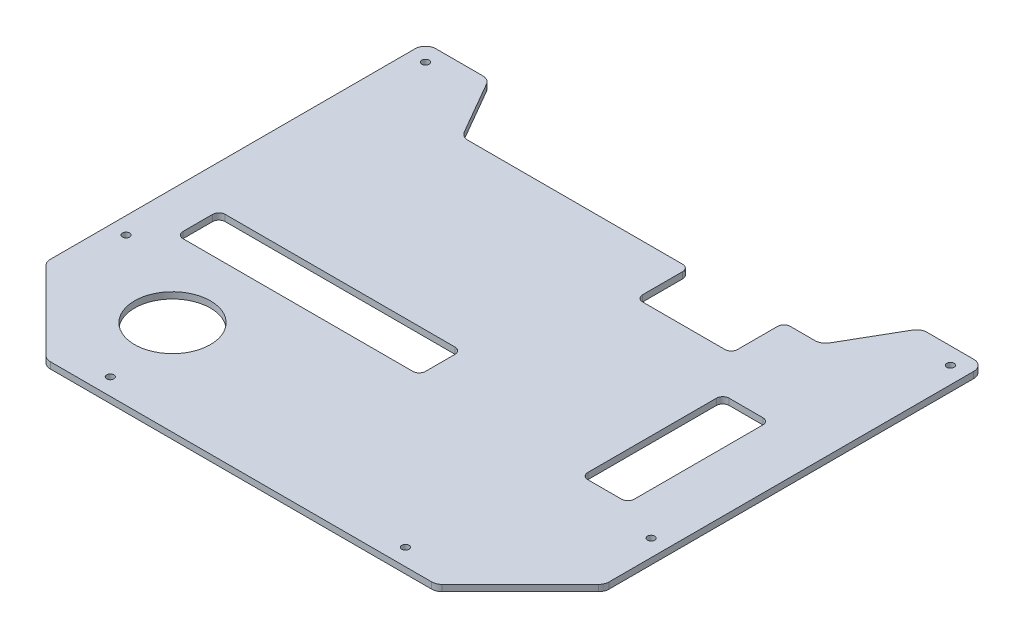
SolidWorks part; units mm, degrees
material "Acier non allié"
ref_plane "Front" through (0, 0, 0) normal (0, 0, 1) x (1, 0, 0)
ref_plane "Top" through (0, 0, 0) normal (0, 1, 0) x (1, 0, 0)
ref_plane "Right" through (0, 0, 0) normal (1, 0, 0) x (0, 0, -1)
sketch "Esquisse1" plane through (0, 0, 0) normal (0, 1, 0) x (1, 0, 0)
  line L0 (0, 0) -> (0, 1919.0564) construction
  line L1 (-92.5, 0) -> (92.5, 0)
  line L2 (92.5, 0) -> (132.5, 40)
  line L3 (132.5, 40) -> (132.5, 220)
  line L4 (132.5, 220) -> (102.5, 220)
  line L5 (102.5, 220) -> (85.1795, 190)
  line L6 (85.1795, 190) -> (-85.1795, 190)
  line L7 (-102.5, 220) -> (-85.1795, 190)
  line L8 (-132.5, 220) -> (-102.5, 220)
  line L9 (-132.5, 40) -> (-132.5, 220)
  line L10 (-92.5, 0) -> (-132.5, 40)
  point P12 (0, 190)
  dimension "D1" = 132.5
  dimension "D2" = 220
  dimension "D3" = 30
  dimension "D4" = 30
  dimension "D5" = 40
  dimension "D6" = 40
  dimension "D7" = 60
extrude "Boss.-Extru.1" add sketch "Esquisse1" along normal blind 3
fillet "Congé1" radius 5 10 edges at (132.5, 1.5, -220) (102.5, 1.5, -220) (85.1795, 1.5, -190) (-85.1795, 1.5, -190) (-102.5, 1.5, -220) (-132.5, 1.5, -220) (-132.5, 1.5, -40) (-92.5, 1.5, 0) (92.5, 1.5, 0) (132.5, 1.5, -40)
sketch "Esquisse2" plane through (0, 0, 0) normal (0, -1, 0) x (1, 0, 0)
  line L0 (0, 0) -> (0, -330.9968) construction
  line L1 (-90.4289, 0) -> (90.4289, 0) construction
  line L2 (-105.3868, -220) -> (-127.5, -220) construction
  line L3 (-132.5, -215) -> (-132.5, -42.0711) construction
  circle A0 centre (-70, -8) radius 1
  circle A1 centre (-124.5, -70) radius 1
  circle A2 centre (-124.5, -212) radius 1
  circle A3 centre (124.5, -212) radius 1
  circle A4 centre (124.5, -70) radius 1
  circle A5 centre (70, -8) radius 1
  dimension "D3" = 2
  dimension "D6" = 2
  dimension "D9" = 2
  dimension "D1" = 70
  dimension "D2" = 8
  dimension "D4" = 124.5
  dimension "D5" = 70
  dimension "D7" = 8
  dimension "D8" = 8
extrude "Enlèv. mat.-Extru.1" cut sketch "Esquisse2" against normal through all
hole_wizard "Dégagement M31" positions "Esquisse3" profile "Esquisse4" hole size "M3" standard "ISO" end condition through all
sketch "Esquisse3" plane through (0, 0, 0) normal (0, -1, 0) x (-1, 0, 0)
  point P0 (-70, 8)
  point P3 (-124.5, 70)
  point P6 (-124.5, 212)
  point P9 (124.5, 212)
  point P12 (124.5, 70)
  point P15 (70, 8)
sketch "Esquisse4" plane through (70, 0, -8) normal (1, 0, 0) x (0, 0, -1)
  line L0 (0, 0) -> (0, 3)
  line L1 (0, 3) -> (1.7, 3)
  line L2 (1.7, 3) -> (1.7, 0)
  line L5 (1.7, 0) -> (0, 0)
  line L11 (0, -6.35) -> (0, 107.95) construction
  dimension "Diamètre du perçage jusqu'au prochain" = 3.4
  dimension "Profondeur du perçage jusqu'au prochain" = 3
sketch "Esquisse5" plane through (0, 0, 0) normal (0, -1, 0) x (1, 0, 0)
  line L6 (82.2927, -190) -> (-82.2927, -190) construction
  line L7 (22.5, -190) -> (67.5, -190)
  line L20 (22.5, -190) -> (22.5, -165)
  line L21 (22.5, -165) -> (67.5, -165)
  line L22 (67.5, -190) -> (67.5, -165)
  line L23 (132.5, -42.0711) -> (132.5, -215) construction
  line L25 (-112.5, -102) -> (2.5, -102)
  line L26 (-112.5, -102) -> (-112.5, -82)
  line L27 (-112.5, -82) -> (2.5, -82)
  line L28 (2.5, -102) -> (2.5, -82)
  line L29 (-132.5, -215) -> (-132.5, -42.0711) construction
  line L30 (127.5, -220) -> (105.3868, -220) construction
  line L31 (82.5, -146) -> (104.5, -146)
  line L32 (82.5, -146) -> (82.5, -79)
  line L33 (82.5, -79) -> (104.5, -79)
  line L34 (104.5, -146) -> (104.5, -79)
  line L35 (-90.4289, 0) -> (90.4289, 0) construction
  circle A0 centre (-77.5, -45) radius 18
  dimension "D14" = 36
  dimension "D1" = 65
  dimension "D2" = 110
  dimension "D3" = 25
  dimension "D4" = 82
  dimension "D5" = 135
  dimension "D6" = 20
  dimension "D7" = 115
  dimension "D8" = 50
  dimension "D9" = 74
  dimension "D10" = 67
  dimension "D11" = 22
  dimension "D12" = 55
  dimension "D13" = 45
extrude "Enlèv. mat.-Extru.2" cut sketch "Esquisse5" against normal through all
fillet "Congé2" radius 3 12 edges at (67.5, 1.5, -190) (67.5, 1.5, -165) (22.5, 1.5, -165) (22.5, 1.5, -190) (104.5, 1.5, -146) (82.5, 1.5, -146) (82.5, 1.5, -79) (104.5, 1.5, -79) (2.5, 1.5, -82) (2.5, 1.5, -102) (-112.5, 1.5, -82) (-112.5, 1.5, -102)
equation "\"WIDTH\"= 300mm'Total width of the robot"
equation "\"LENGTH\"= 220mm'Total length of the robot"
equation "\"CUT_DEPTH\"= 45mm'Depth of the cut on the edges of the plate"
equation "\"Plate_th\"= 3mm'Thickness of the plate"
equation "\"D1\"= \"Plate_th\""
